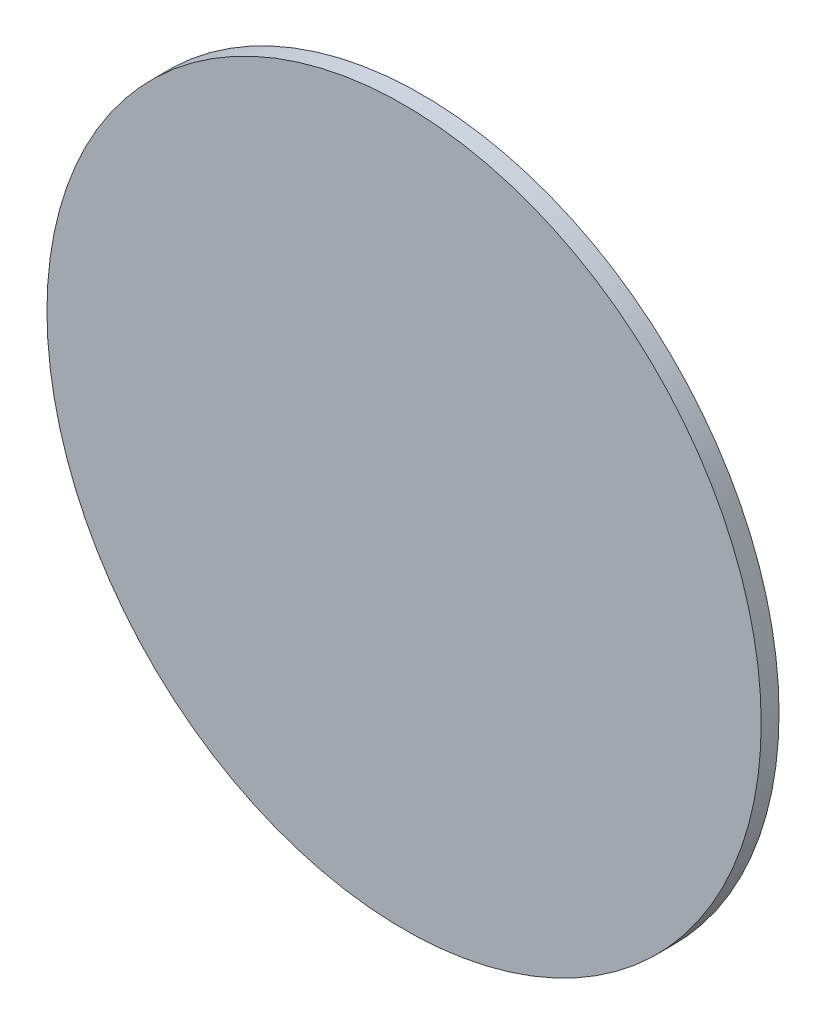
SolidWorks part; units mm, degrees
material "Corrugated Paper"
ref_plane "Front Plane" through (0, 0, 0) normal (0, 0, 1) x (1, 0, 0)
ref_plane "Top Plane" through (0, 0, 0) normal (0, 1, 0) x (1, 0, 0)
ref_plane "Right Plane" through (0, 0, 0) normal (1, 0, 0) x (0, 0, -1)
sketch "Sketch1" plane through (0, 0, 0) normal (0, 0, 1) x (1, 0, 0)
  circle A0 centre (0, 0) radius 95.25
extrude "Boss-Extrude1" add sketch "Sketch1" along normal blind 4.7625
sketch "Sketch2" plane through (0, 0, 4.7625) normal (0, 0, 1) x (1, 0, 0)
  line L0 (95.25, 0) -> (0, 0) construction
  line L1 (0, 0) -> (0, 95.25) construction
  circle A0 centre (0, 0) radius 95.25 construction
ref_axis "Axis1" through (0, 0, 4.7625) along (0, 1, 0)
ref_axis "Axis2" through (95.25, 0, 4.7625) along (-1, 0, 0)
